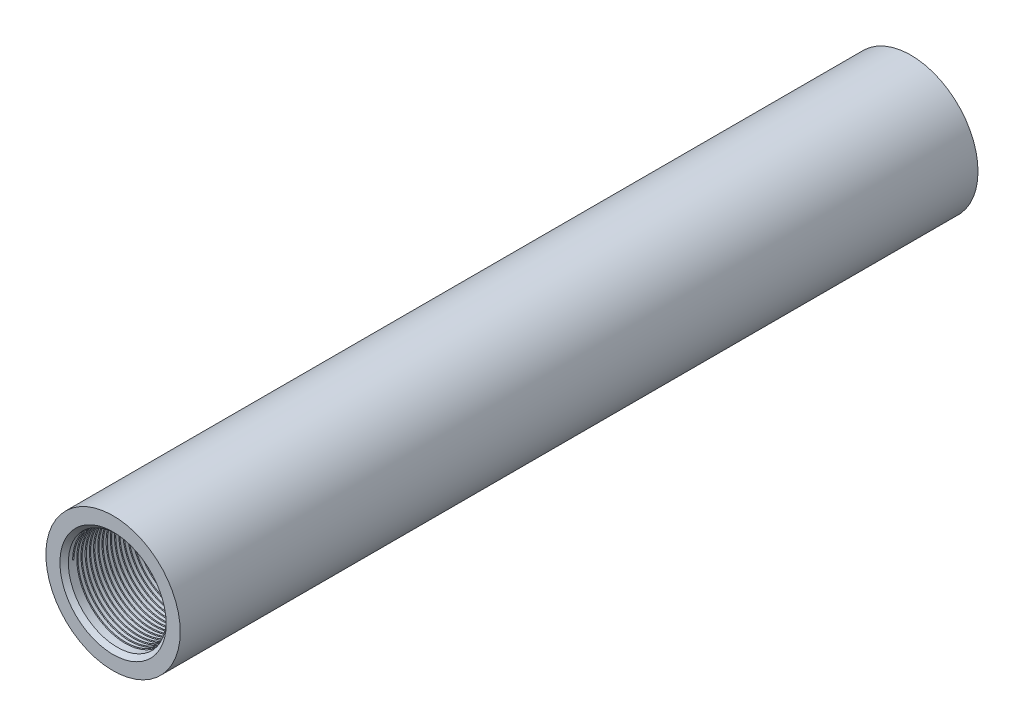
SolidWorks part; units mm, degrees
ref_plane "Ön Düzlem" through (0, 0, 0) normal (0, 0, 1) x (1, 0, 0)
ref_plane "Üst Düzlem" through (0, 0, 0) normal (0, 1, 0) x (1, 0, 0)
ref_plane "Sağ Düzlem" through (0, 0, 0) normal (1, 0, 0) x (0, 0, -1)
sketch "Çizim1" plane through (0, 0, 0) normal (0, 0, 1) x (1, 0, 0)
  circle A0 centre (0, 0) radius 16
  circle A1 centre (0, 0) radius 11.65
  dimension "D1" = 32
  dimension "D2" = 4.35
extrude "Yükseklik-Ekstrüzyon1" add sketch "Çizim1" along normal blind 190
chamfer "Pah1" distance 1 angle 45 1 edges at (11.65, 0, 190)
thread "Diş1" pitch 0.3175 method extrude profile "Diş Profili2" start angle 0, offset 1, length 20, pitch 1, diameter 23.3
ref_plane "Düzlem2" through (-11.65, 0, 188) normal (0, -1, 0) x (-1, 0, 0)
sketch "Diş Profili2" plane through (-11.65, 0, 188) normal (0, -1, 0) x (-1, 0, 0)
  line L0 (0, 0) -> (0, 0.3175) construction
  line L11 (0, 0) -> (0, 0.2778)
  line L12 (0, 0.2778) -> (-0.1719, 0.1786)
  line L13 (-0.1719, 0.1786) -> (-0.1719, 0.0992)
  line L15 (-0.1719, 0.0992) -> (0, 0)
  line L17 (-0.1719, 0.1389) -> (0, 0.1389) construction
  point P2 (0, 0)
  dimension "Pitch" = 0.3175
  dimension "Profile_Angle" = 60
  dimension "Profile_Land" = 0.0794
  dimension "Profile_Height" = 0.1719
chamfer "Pah2" distance 1 angle 45 1 edges at (11.65, 0, 0)
thread "Diş2" pitch 0.3175 method extrude profile "Diş Profili3" start angle 0, offset 0, length 20, pitch 1, diameter 23.3
ref_plane "Düzlem3" through (11.65, 0, 1) normal (0, -1, 0) x (1, 0, 0)
sketch "Diş Profili3" plane through (11.65, 0, 1) normal (0, -1, 0) x (1, 0, 0)
  line L0 (0, 0) -> (0, 0.3175) construction
  line L11 (0, 0) -> (0, 0.2778)
  line L12 (0, 0.2778) -> (-0.1719, 0.1786)
  line L13 (-0.1719, 0.1786) -> (-0.1719, 0.0992)
  line L15 (-0.1719, 0.0992) -> (0, 0)
  line L17 (-0.1719, 0.1389) -> (0, 0.1389) construction
  point P2 (0, 0)
  dimension "Pitch" = 0.3175
  dimension "Profile_Angle" = 60
  dimension "Profile_Land" = 0.0794
  dimension "Profile_Height" = 0.1719
